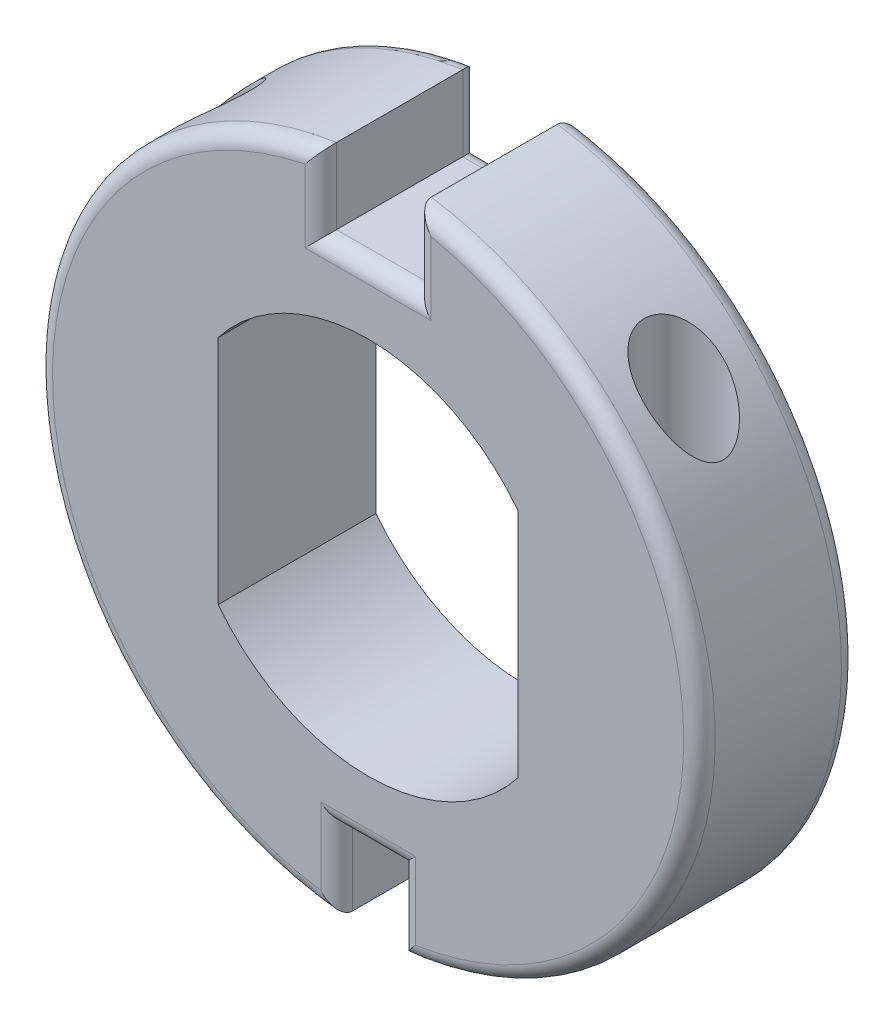
SolidWorks part; units mm, degrees
ref_plane "Plan de face" through (0, 0, 0) normal (0, 0, 1) x (1, 0, 0)
ref_plane "Plan de dessus" through (0, 0, 0) normal (0, 1, 0) x (1, 0, 0)
ref_plane "Plan de droite" through (0, 0, 0) normal (1, 0, 0) x (0, 0, -1)
sketch "Esquisse1" plane through (0, 0, 0) normal (0, 0, 1) x (1, 0, 0)
  line L0 (0, -21) -> (0, 21) construction
  line L1 (3, 16) -> (-3, 16)
  line L2 (-3, 16) -> (-3, 20.7846)
  line L3 (2, -15.9045) -> (-2, -15.9045)
  line L4 (-2, -15.9045) -> (-2, -20.9045)
  line L5 (-21, 0) -> (21, 0)
  line L6 (3, 16) -> (3, 20.7846)
  line L7 (2, -15.9045) -> (2, -20.9045)
  line L9 (9.5, -7.3314) -> (-9.5, -7.3314)
  line L10 (9.5, -7.3314) -> (9.5, 7.3314)
  line L11 (9.5, 7.3314) -> (-9.5, 7.3314)
  line L12 (-9.5, -7.3314) -> (-9.5, 7.3314)
  line L13 (9.5, -7.3314) -> (-9.5, 7.3314) construction
  line L14 (9.5, 7.3314) -> (-9.5, -7.3314) construction
  circle A0 centre (0, 0) radius 21
  circle A1 centre (0, 0) radius 12
  point P16 (0, 16)
  point P17 (0, -15.9045)
  dimension "D1" = 42
  dimension "D2" = 24
  dimension "D3" = 3
  dimension "D4" = 5
  dimension "D5" = 2
  dimension "D6" = 5
  dimension "D7" = 19
extrude "Boss.-Extru.1" add sketch "Esquisse1" along normal blind 10 contours A1 L5 A0 L4 L3 L7 | A1 L5 A0 L6 L1 L2 | L5 A1 L10 | L10 A1 L5 | L5 A1 L12 | L12 A1 L5 region at (3.4686, 18.3923, 0) region at (15.1931, -13.8089, 0) region at (10.5095, -2.792, 0) region at (10.5095, 2.792, 0) region at (-10.5095, 2.792, 0) region at (-10.5095, -2.792, 0)
sketch "Esquisse2" plane through (0, 0, 0) normal (0, 1, 0) x (1, 0, 0)
  line L0 (0, -10) -> (0, 0) construction
  line L1 (2, -10) -> (-2, -10) construction
  line L2 (-21, -5) -> (21, -5) construction
  line L3 (-21, 0) -> (-21, -10) construction
  line L4 (21, -10) -> (21, 0) construction
  circle A0 centre (15, -5) radius 1.25
  circle A1 centre (15, -5) radius 2.5
  circle A2 centre (-15, -5) radius 2.5
  circle A3 centre (-15, -5) radius 1.25
  dimension "D2" = 2.5
  dimension "D3" = 5
  dimension "D1" = 15
extrude "Enlèv. mat.-Extru.1" cut sketch "Esquisse2" against normal blind 10 and the other way blind 20 contours A0 | A3 region at (15, 0, 5) region at (-15, 0, 5)
extrude "Enlèv. mat.-Extru.2" cut sketch "Esquisse2<5>" along normal blind 10 from offset 7.5 contours A1 A0 | A2 | A3 region at (12.5707, 0, 5)
sketch "Esquisse2<5>" plane through (0, 0, 0) normal (0, 1, 0) x (1, 0, 0) same geometry as "Esquisse2"
fillet "Congé1" radius 1 16 edges at (-2, -18.4045, 0) (0, -15.9045, 0) (2, -18.4045, 0) (-20.994, -0.5036, 0) (-3, 18.3923, 0) (0, 16, 0) (3, 18.3923, 0) (20.994, -0.5036, 0) (-2, -18.4045, 10) (0, -15.9045, 10) (2, -18.4045, 10) (-3, 18.3923, 10) (0, 16, 10) (3, 18.3923, 10) (20.994, -0.5036, 10) (-20.994, -0.5036, 10)
